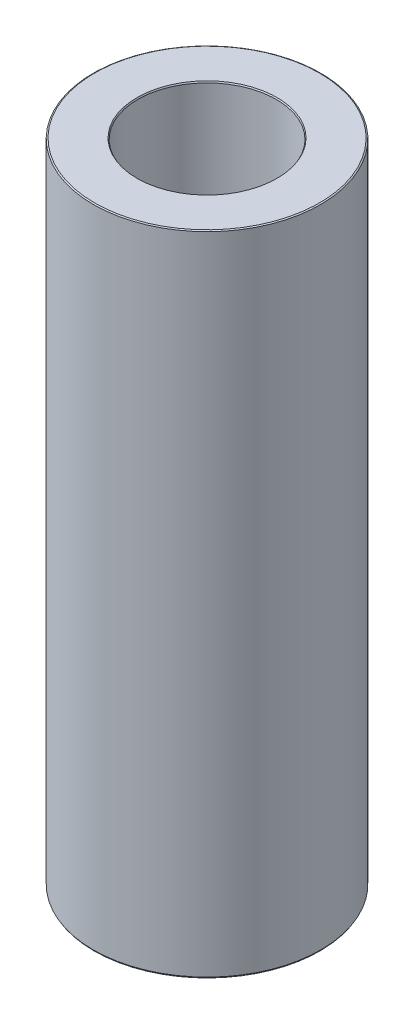
SolidWorks part; units mm, degrees
ref_plane "Front Plane" through (0, 0, 0) normal (0, 0, 1) x (1, 0, 0)
ref_plane "Top Plane" through (0, 0, 0) normal (0, 1, 0) x (1, 0, 0)
ref_plane "Right Plane" through (0, 0, 0) normal (1, 0, 0) x (0, 0, -1)
sketch "Sketch1" plane through (0, 0, 0) normal (0, 1, 0) x (1, 0, 0)
  circle A0 centre (0, 0) radius 45
  dimension "SLEEVE_OD" = 90
extrude "Boss-Extrude1" add sketch "Sketch1" along normal blind 256.1974
sketch "Sketch2" plane through (0, 0, 0) normal (0, 1, 0) x (1, 0, 0)
  circle A0 centre (0, 0) radius 27.4117
  dimension "BORE_D" = 54.8234
extrude "Cut-Extrude1" cut sketch "Sketch2" along normal through all
chamfer "Chamfer1" distance 0.2906 angle 60 4 edges at (0, 256.1974, 27.4117) (0, 0, 27.4117) (0, 0, 45) (0, 256.1974, 45) first distance on face at (0, 256.1974, 27.4117) first distance on face at (0, 0, 27.4117) first distance on face at (0, 256.1974, 45)
